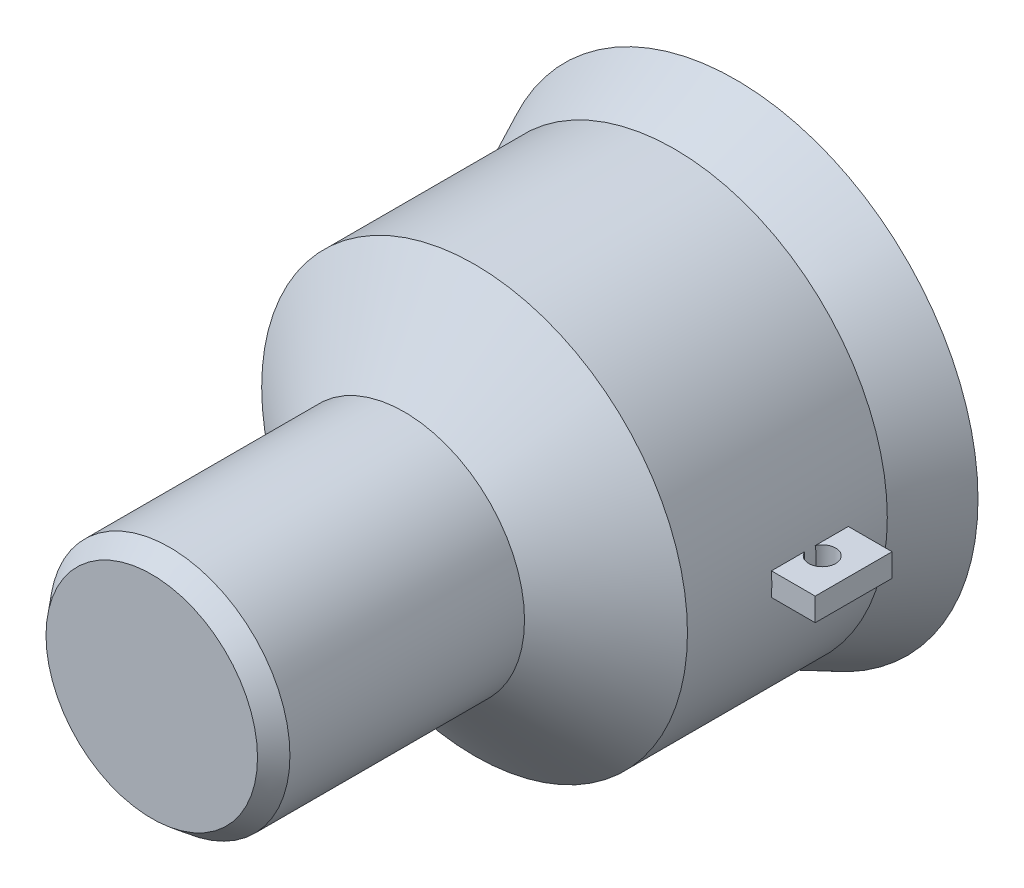
SolidWorks part; units mm, degrees
ref_plane "前视基准面" through (0, 0, 0) normal (0, 0, 1) x (1, 0, 0)
ref_plane "上视基准面" through (0, 0, 0) normal (0, 1, 0) x (1, 0, 0)
ref_plane "右视基准面" through (0, 0, 0) normal (1, 0, 0) x (0, 0, -1)
sketch "草图1" plane through (0, 0, 0) normal (0, 1, 0) x (1, 0, 0)
  line L0 (0, 0) -> (0, 102.5516) construction
  line L1 (25.35, 72.3135) -> (31.5, 72.3135)
  line L3 (27.7, 38.3135) -> (27.7, 64.3135)
  line L4 (27.7, 64.3135) -> (31.5, 72.3135)
  line L5 (25.35, 72.3135) -> (25.35, 38.3135)
  line L6 (25.35, 38.3135) -> (13, 28.1275)
  line L7 (27.7, 38.3135) -> (15.6413, 29.172)
  line L9 (15.6413, 29.172) -> (15.6413, -1.3495)
  line L10 (15.6413, -1.3495) -> (13.7602, -3.6865)
  line L11 (13.7602, -3.6865) -> (0, -3.6865)
  line L12 (13, 28.1275) -> (0, 28.1275)
  line L13 (0, 28.1275) -> (0, -3.6865)
  point P12 (28.425, 72.3135)
  dimension "D1" = 13
  dimension "D2" = 2.35
  dimension "D3" = 8
  dimension "D4" = 25.35
  dimension "D5" = 3
  dimension "D6" = 76
  dimension "D7" = 34
  dimension "D8" = 27.7
  dimension "D9" = 31.5
revolve "旋转1" add sketch "草图1" angle 360 about L0
sketch "草图2" plane through (0, 0, 0) normal (0, 1, 0) x (1, 0, 0)
  line L0 (0, 72.3135) -> (0, 52.7747) construction
  line L1 (25.1829, 59.2826) -> (33.35, 59.2826)
  line L2 (25.1829, 59.2826) -> (25.1829, 49.2826)
  line L3 (25.1829, 49.2826) -> (33.35, 49.2826)
  line L4 (33.35, 59.2826) -> (33.35, 49.2826)
  line L5 (25.1829, 59.2826) -> (33.35, 49.2826) construction
  line L6 (25.1829, 49.2826) -> (33.35, 59.2826) construction
  line L7 (25.35, 72.3135) -> (-25.35, 72.3135) construction
  line L8 (-25.1829, 49.2826) -> (-33.35, 59.2826) construction
  line L9 (-25.1829, 59.2826) -> (-33.35, 49.2826) construction
  line L10 (-33.35, 59.2826) -> (-33.35, 49.2826)
  line L11 (-25.1829, 49.2826) -> (-33.35, 49.2826)
  line L12 (-25.1829, 59.2826) -> (-25.1829, 49.2826)
  line L13 (-25.1829, 59.2826) -> (-33.35, 59.2826)
  circle A0 centre (29.2664, 54.2826) radius 1.75
  circle A1 centre (-29.2664, 54.2826) radius 1.75
  dimension "D1" = 3.5
  dimension "D2" = 10
  dimension "D3" = 33.35
extrude "凸台-拉伸1" add sketch "草图2" along normal blind 1.5 and the other way blind 1.5
